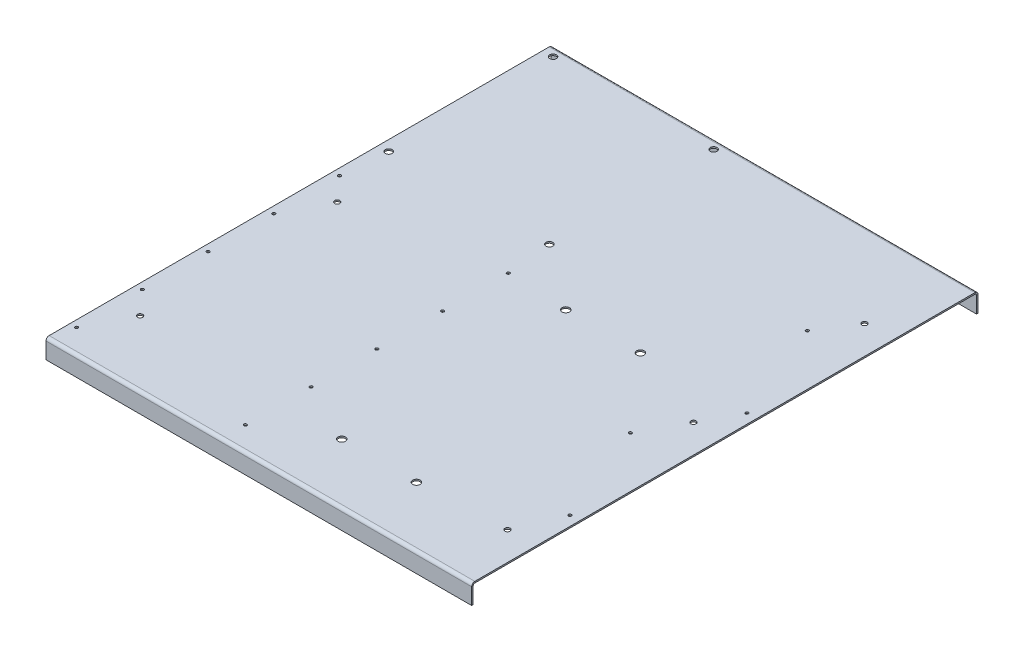
SolidWorks part; units mm, degrees
note: The reader was unsure of these and kept them because the rebuilt part matched: flange length of "Ребро-кромка1".
ref_plane "Спереди" through (0, 0, 0) normal (0, 0, 1) x (1, 0, 0)
ref_plane "Сверху" through (0, 0, 0) normal (0, 1, 0) x (1, 0, 0)
ref_plane "Справа" through (0, 0, 0) normal (1, 0, 0) x (0, 0, -1)
sketch "Эскиз1" plane through (0, 0, 0) normal (0, 1, 0) x (1, 0, 0)
  line L1 (-31.9779, 35.0297) -> (253.0221, 35.0297)
  line L2 (-31.9779, 35.0297) -> (-31.9779, -301.9703)
  line L3 (-31.9779, -301.9703) -> (253.0221, -301.9703)
  line L4 (253.0221, 35.0297) -> (253.0221, -301.9703)
  dimension "D1" = 285
  dimension "D2" = 337
sheet metal parameters "Листовой металл1" thickness 1 parameters "D1"=1.1
base flange "Базовая кромка1" sketch "Эскиз1" thickness 1 reverse thickness direction no parameters "D1"=1.1
edge flange "Ребро-кромка1" sketch "Эскиз8" flange profiles "Эскиз8", "Эскиз9" flange angle 90 flange length 12 flange position material outside bend radius 1.1 thickness 1 relief rectangular parameters "D6"=10, "D8"=1
sketch "Эскиз8" plane through (0, -1, 301.9703) normal (0, 0, 1) x (-1, 0, 0)
  line L0 (31.9779, 0) -> (-253.0221, 0) construction
  line L1 (31.9779, 0) -> (-253.0221, 0)
  line L2 (-253.0221, 0) -> (-253.0221, 12)
  line L3 (-253.0221, 12) -> (31.9779, 12)
  line L4 (31.9779, 12) -> (31.9779, 0)
sketch "Эскиз9" plane through (0, -1, -35.0297) normal (0, 0, -1) x (1, 0, 0)
  line L0 (253.0221, 0) -> (-31.9779, 0) construction
  line L1 (253.0221, 0) -> (-31.9779, 0)
  line L2 (-31.9779, 0) -> (-31.9779, 12)
  line L3 (-31.9779, 12) -> (253.0221, 12)
  line L4 (253.0221, 12) -> (253.0221, 0)
bend "EdgeBend1" bend radius 1.1 bend angle 90 parameters "D5"=1
bend "EdgeBend2" bend radius 1.1 bend angle 90 parameters "D5"=2
sketch "Эскиз10" plane through (0, 0, 0) normal (0, 1, 0) x (1, 0, 0)
  line L0 (221.2221, -44.2203) -> (216.8221, -44.2203) construction
  line L1 (221.2221, -46.4203) -> (221.2221, -42.0203) construction
  line L2 (216.8221, -44.2203) -> (219.0221, -39.8203) construction
  line L3 (219.0221, -39.8203) -> (219.0221, -48.6203) construction
  line L4 (246.5221, -107.8203) -> (246.5221, -116.6203) construction
  line L5 (246.5221, -116.6203) -> (248.7221, -112.2203) construction
  line L6 (248.7221, -114.4203) -> (248.7221, -110.0203) construction
  line L7 (248.7221, -112.2203) -> (244.3221, -112.2203) construction
  line L8 (244.3221, -110.0203) -> (244.3221, -114.4203) construction
  line L9 (219.0221, -158.3203) -> (219.0221, -167.1203) construction
  line L10 (219.0221, -167.1203) -> (221.2221, -162.7203) construction
  line L11 (221.2221, -164.9203) -> (221.2221, -160.5203) construction
  line L12 (221.2221, -162.7203) -> (216.8221, -162.7203) construction
  line L13 (216.8221, -160.5203) -> (216.8221, -164.9203) construction
  line L14 (246.5221, -226.3203) -> (246.5221, -235.1203) construction
  line L15 (246.5221, -235.1203) -> (248.7221, -230.7203) construction
  line L16 (248.7221, -232.9203) -> (248.7221, -228.5203) construction
  line L17 (248.7221, -230.7203) -> (244.3221, -230.7203) construction
  line L18 (244.3221, -228.5203) -> (244.3221, -232.9203) construction
  line L19 (216.8221, -42.0203) -> (216.8221, -46.4203) construction
  circle A0 centre (-27.4779, -110.9703) radius 1
  circle A1 centre (85.5221, -110.9703) radius 1
  circle A2 centre (85.5221, -154.9703) radius 1
  circle A3 centre (-27.4779, -154.9703) radius 1
  circle A4 centre (-27.4779, -198.9703) radius 1
  circle A5 centre (85.5221, -198.9703) radius 1
  circle A6 centre (-27.4779, -242.9703) radius 1
  circle A7 centre (85.5221, -242.9703) radius 1
  circle A8 centre (85.5221, -286.9703) radius 1
  circle A9 centre (-27.4779, -286.9703) radius 1
  arc A10 (221.2221, -42.0203) -> (216.8221, -42.0203) centre (219.0221, -42.0203) ccw construction
  arc A11 (216.8221, -46.4203) -> (221.2221, -46.4203) centre (219.0221, -46.4203) ccw construction
  arc A12 (248.7221, -110.0203) -> (244.3221, -110.0203) centre (246.5221, -110.0203) ccw construction
  arc A13 (244.3221, -114.4203) -> (248.7221, -114.4203) centre (246.5221, -114.4203) ccw construction
  arc A14 (221.2221, -160.5203) -> (216.8221, -160.5203) centre (219.0221, -160.5203) ccw construction
  arc A15 (216.8221, -164.9203) -> (221.2221, -164.9203) centre (219.0221, -164.9203) ccw construction
  arc A16 (248.7221, -228.5203) -> (244.3221, -228.5203) centre (246.5221, -228.5203) ccw construction
  arc A17 (244.3221, -232.9203) -> (248.7221, -232.9203) centre (246.5221, -232.9203) ccw construction
  circle A18 centre (246.5221, -230.7203) radius 1
  circle A19 centre (219.0221, -162.7203) radius 1
  circle A20 centre (246.5221, -112.2203) radius 1
  circle A21 centre (219.0221, -44.2203) radius 1
  dimension "D1" = 2
  dimension "D2" = 2
  dimension "D3" = 2
  dimension "D4" = 2
  dimension "D5" = 2
  dimension "D6" = 2
  dimension "D7" = 2
  dimension "D8" = 2
  dimension "D9" = 2
  dimension "D10" = 2
  dimension "D11" = 2
  dimension "D12" = 2
  dimension "D13" = 2
  dimension "D14" = 2
extrude "Вырез-Вытянуть1" cut sketch "Эскиз10" against normal blind 10 normal cut yes
sketch "Эскиз11" plane through (0, 0, 0) normal (0, 1, 0) x (1, 0, 0)
  circle A0 centre (82.5221, 29.5297) radius 2.25
  circle A1 centre (82.5221, -80.4703) radius 2.25
  circle A2 centre (-24.9779, -80.4703) radius 2.25
  circle A3 centre (-24.9779, 29.5297) radius 2.25
  dimension "D1" = 4.5
  dimension "D2" = 4.5
  dimension "D3" = 4.5
  dimension "D4" = 4.5
extrude "Вырез-Вытянуть2" cut sketch "Эскиз11" against normal blind 3 normal cut yes
sketch "Эскиз12" plane through (0, 0, 0) normal (0, 1, 0) x (1, 0, 0)
  line L0 (-12.9779, -125.4723) -> (-12.9779, -325.107) construction
  line L1 (234.0221, -14.4079) -> (234.0221, -321.358) construction
  line L2 (253.0221, -300.8703) -> (253.0221, 33.9297) construction
  line L3 (-31.9779, 33.9297) -> (-31.9779, -300.8703) construction
  line L4 (79.0221, -121.9703) -> (-20.9779, -121.9703) construction
  line L9 (88.0221, -263.9703) -> (-29.9779, -263.9703) construction
  line L10 (251.0221, -38.9703) -> (214.5221, -38.9703) construction
  line L11 (251.0221, -117.4703) -> (214.5221, -117.4703) construction
  line L12 (227.6221, -274.9703) -> (240.5221, -274.9703) construction
  circle A0 centre (-12.9779, -126.9703) radius 1.75
  circle A1 centre (234.0221, -20.9703) radius 1.75
  circle A2 centre (234.0221, -135.4703) radius 1.75
  circle A3 centre (-12.9779, -258.9703) radius 1.75
  circle A4 centre (234.0221, -259.9703) radius 1.75
  dimension "D3" = 5
  dimension "D4" = 3.5
  dimension "D5" = 18
  dimension "D6" = 3.5
  dimension "D7" = 18
  dimension "D8" = 3.5
  dimension "D9" = 5
  dimension "D10" = 3.5
  dimension "D11" = 3.5
  dimension "D12" = 15
  dimension "D1" = 19
  dimension "D2" = 19
extrude "Вырез-Вытянуть3" cut sketch "Эскиз12" against normal blind 3 normal cut yes
sketch "Эскиз13" plane through (0, -1, 0) normal (0, -1, 0) x (1, 0, 0)
  circle A0 centre (126.0221, 262.9703) radius 2.5
  circle A1 centre (176.0221, 262.9703) radius 2.5
  circle A2 centre (126.0221, 112.9703) radius 2.5
  circle A3 centre (176.0221, 112.9703) radius 2.5
  dimension "D1" = 5
  dimension "D2" = 5
  dimension "D3" = 5
  dimension "D4" = 5
extrude "Вырез-Вытянуть4" cut sketch "Эскиз13" against normal blind 10 normal cut yes
flat pattern "Развертка1" [suppressed]
sketch "Сгиб-Линии1" plane through (0, 0, 0) normal (0, 1, 0) x (1, 0, 0)
sketch3d "Граничная рамка1" [suppressed]
  line L0 (31.9779, 35.0297, 0) -> (31.9779, -270.9703, 0) construction
  line L1 (-253.0221, 35.0297, 0) -> (-253.0221, -270.9703, 0) construction
  line L2 (31.9779, 35.0297, 0) -> (-253.0221, 35.0297, 0) construction
  line L3 (31.9779, -270.9703, 0) -> (-253.0221, -270.9703, 0) construction
bend of the flat pattern "Плоское состояние-<EdgeBend1>1"
bend of the flat pattern "Плоское состояние-<EdgeBend2>1"
